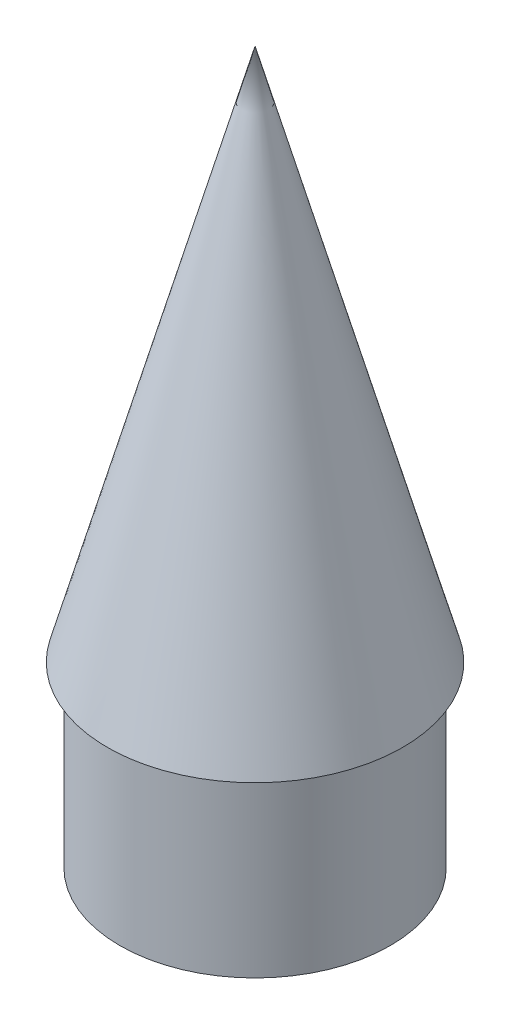
SolidWorks part; units mm, degrees
ref_plane "Front Plane" through (0, 0, 0) normal (0, 0, 1) x (1, 0, 0)
ref_plane "Top Plane" through (0, 0, 0) normal (0, 1, 0) x (1, 0, 0)
ref_plane "Right Plane" through (0, 0, 0) normal (1, 0, 0) x (0, 0, -1)
sketch "Sketch1" plane through (0, 0, 0) normal (0, 0, 1) x (1, 0, 0)
  line L1 (0, 150) -> (-41.5, 0)
  line L2 (-41.5, 0) -> (-33, 0)
  line L3 (0, 142.4995) -> (-38.8715, 2)
  line L4 (-38.8715, 2) -> (-33, 2)
  line L6 (0, 142.4995) -> (0, 150)
  line L7 (0, 2) -> (0, 142.4995) construction
  line L8 (-33, 2) -> (-33, 0)
  line L9 (0, 0) -> (-25.623, 0) construction
  dimension "D1" = 41.5
  dimension "D2" = 150
  dimension "D3" = 2
  dimension "D4" = 2
  dimension "D5" = 2
  dimension "D6" = 2
  dimension "D7" = 33
revolve "Revolve3" add sketch "Sketch1" angle 360 about L7
sketch "Sketch2" plane through (0, 0, 0) normal (0, 0, 1) x (1, 0, 0)
  line L0 (33, 30.7229) -> (33, -50)
  line L1 (41.5, 0) -> (0, 150) construction
  line L2 (33, -50) -> (38, -50)
  line L3 (38, -50) -> (38, 0)
  line L5 (0, 0) -> (0, -76.9883) construction
  line L6 (-41.5, 0) -> (41.5, 0) construction
  line L7 (-41.5, 0) -> (33, 0) construction
  line L8 (41.5, 0) -> (0, 150)
  line L9 (33, 30.7229) -> (38, 12.6506)
  line L10 (33, 30.7229) -> (41.5, 0)
  line L11 (38, 0) -> (41.5, 0)
  line L12 (33, 0) -> (38, 0) construction
  dimension "D1" = 38
  dimension "D2" = 5
  dimension "D3" = 50
revolve "Revolve6" add sketch "Sketch2" angle 360 about L5 region at (35.6144, -12.909, 0)
